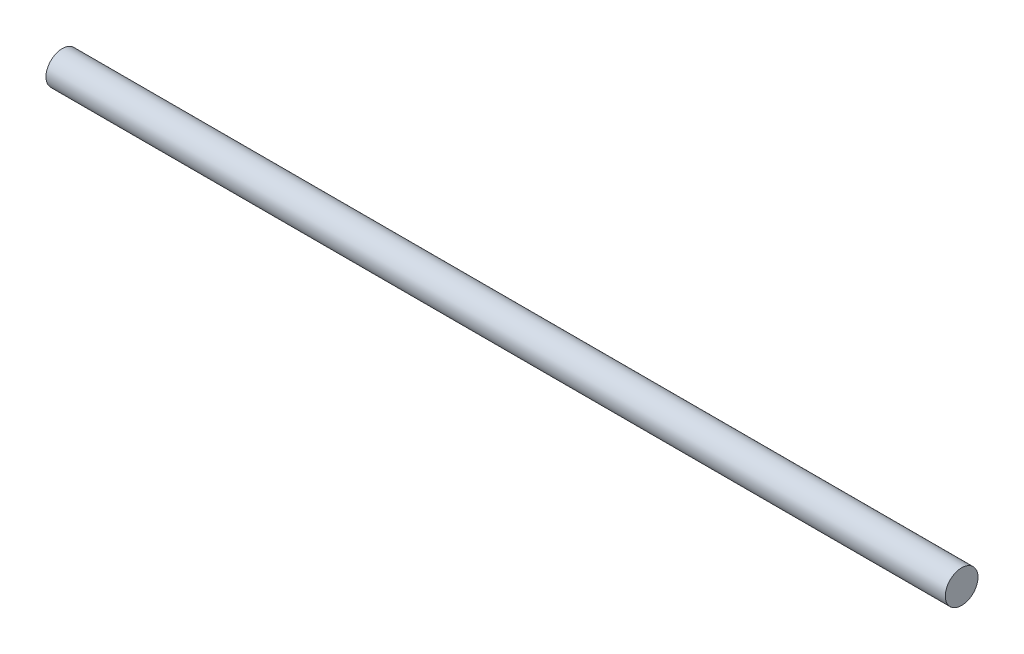
SolidWorks part; units mm, degrees
ref_plane "Front Plane" through (0, 0, 0) normal (0, 0, 1) x (1, 0, 0)
ref_plane "Top Plane" through (0, 0, 0) normal (0, 1, 0) x (1, 0, 0)
ref_plane "Right Plane" through (0, 0, 0) normal (1, 0, 0) x (0, 0, -1)
sketch "Sketch1" plane through (0, 0, 0) normal (1, 0, 0) x (0, 0, -1)
  circle A0 centre (0, 0) radius 0.5
  dimension "D1" = 1
extrude "Boss-Extrude1" add sketch "Sketch1" along normal blind 13.75 and the other way blind 13.75
